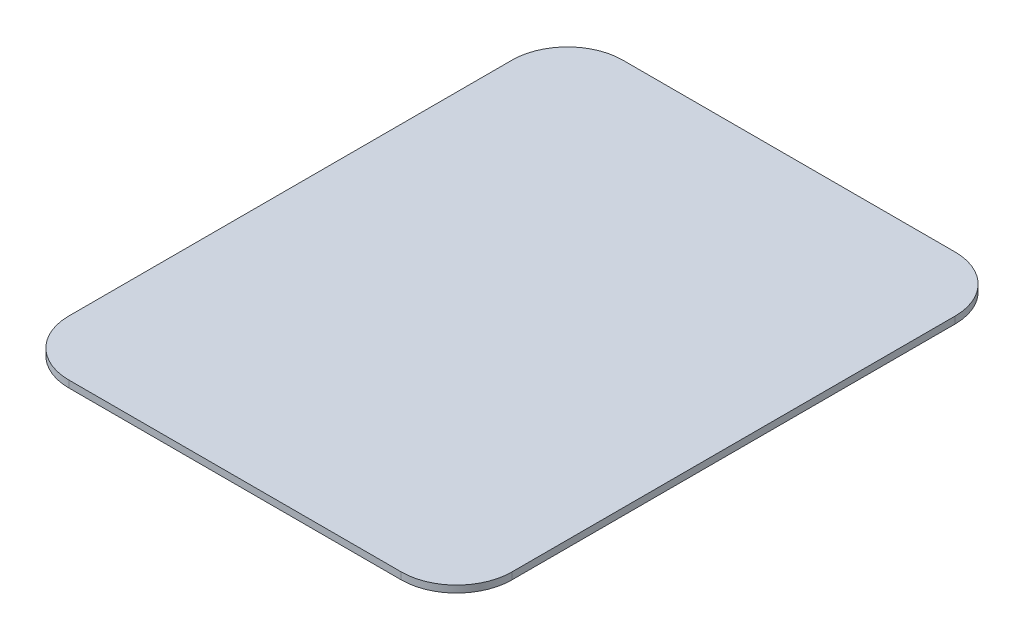
SolidWorks part; units mm, degrees
material "Plain Carbon Steel"
ref_plane "Front" through (0, 0, 0) normal (0, 0, 1) x (1, 0, 0)
ref_plane "Top" through (0, 0, 0) normal (0, 1, 0) x (1, 0, 0)
ref_plane "Right" through (0, 0, 0) normal (1, 0, 0) x (0, 0, -1)
sketch "Sketch1" plane through (0, 0, 0) normal (0, 1, 0) x (1, 0, 0)
  line L1 (-101.6, -127) -> (101.6, -127)
  line L2 (-101.6, -127) -> (-101.6, 127)
  line L3 (-101.6, 127) -> (101.6, 127)
  line L4 (101.6, -127) -> (101.6, 127)
  line L5 (-101.6, -127) -> (101.6, 127) construction
  line L6 (-101.6, 127) -> (101.6, -127) construction
  point P0 (0, 0)
  dimension "D1" = 254
  dimension "D2" = 203.2
extrude "Boss-Extrude1" add sketch "Sketch1" along normal blind 3.175
fillet "Fillet1" radius 25.4 4 edges at (-101.6, 1.5875, -127) (-101.6, 1.5875, 127) (101.6, 1.5875, -127) (101.6, 1.5875, 127)
